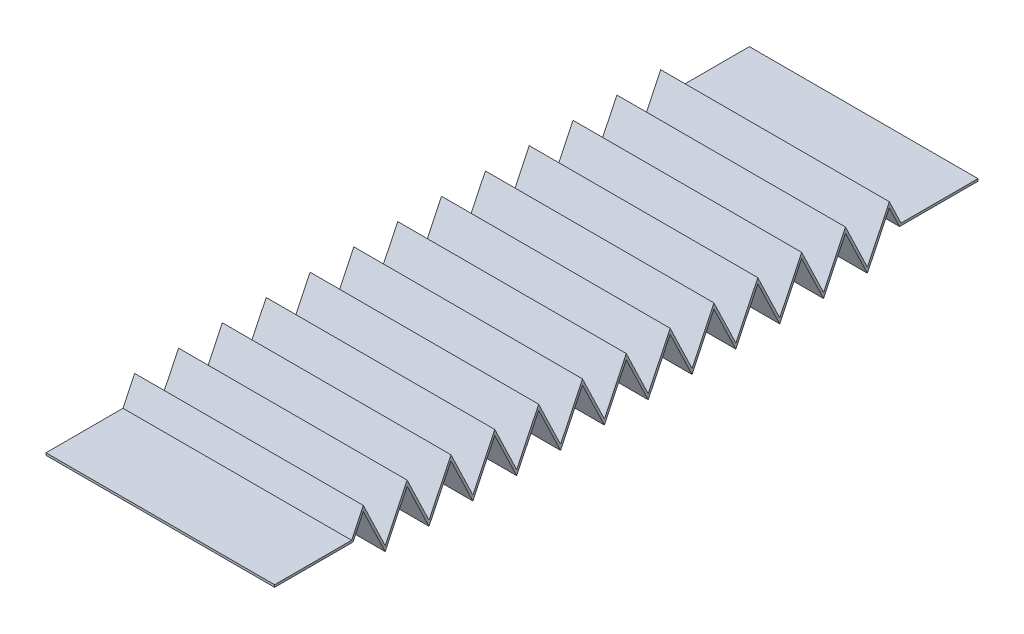
SolidWorks part; units mm, degrees
ref_plane "Front Plane" through (0, 0, 0) normal (0, 0, 1) x (1, 0, 0)
ref_plane "Top Plane" through (0, 0, 0) normal (0, 1, 0) x (1, 0, 0)
ref_plane "Right Plane" through (0, 0, 0) normal (1, 0, 0) x (0, 0, -1)
sketch "Sketch2" plane through (0, 0, 0) normal (0, 0, 1) x (1, 0, 0)
  line L1 (-27.5, 10) -> (27.5, 10)
  line L2 (-27.5, 10) -> (-27.5, 0)
  line L3 (-27.5, 0) -> (27.5, 0)
  line L4 (27.5, 10) -> (27.5, 0)
  point P4 (0, 0)
  dimension "D1" = 10
  dimension "D2" = 55
sketch "Sketch3" plane through (0, 0, 0) normal (1, 0, 0) x (0, 0, -1)
  line L0 (0, 10) -> (153.8422, 10) construction
  line L1 (0, 0) -> (153.8422, 0) construction
  line L3 (17, 5) -> (19.3968, 10)
  line L4 (19.3968, 10) -> (24.1905, 0)
  line L5 (24.1905, 0) -> (28.9842, 10)
  line L6 (28.9842, 10) -> (33.7779, 0)
  line L7 (33.7779, 0) -> (38.5716, 10)
  line L8 (38.5716, 10) -> (43.3653, 0)
  line L9 (43.3653, 0) -> (48.159, 10)
  line L10 (48.159, 10) -> (52.9527, 0)
  line L11 (52.9527, 0) -> (57.7464, 10)
  line L12 (57.7464, 10) -> (62.5401, 0)
  line L13 (62.5401, 0) -> (67.3337, 10)
  line L14 (67.3337, 10) -> (72.1274, 0)
  line L15 (72.1274, 0) -> (76.9211, 10)
  line L16 (76.9211, 10) -> (81.7148, 0)
  line L17 (81.7148, 0) -> (86.5085, 10)
  line L18 (86.5085, 10) -> (91.3022, 0)
  line L19 (0, 10) -> (0, 0) construction
  line L20 (91.3022, 0) -> (96.0959, 10)
  line L21 (96.0959, 10) -> (100.8896, 0)
  line L22 (100.8896, 0) -> (105.6833, 10)
  line L23 (105.6833, 10) -> (110.477, 0)
  line L24 (110.477, 0) -> (115.2706, 10)
  line L25 (115.2706, 10) -> (120.0643, 0)
  line L26 (120.0643, 0) -> (124.858, 10)
  line L27 (124.858, 10) -> (129.6517, 0)
  line L28 (129.6517, 0) -> (134.4454, 10)
  line L29 (134.4454, 10) -> (136.8422, 5)
  line L30 (153.8422, 10) -> (153.8422, 0) construction
  line L31 (17, 5) -> (0, 5)
  line L32 (136.8422, 5) -> (153.8422, 5)
  line L33 (153.8422, -12.75) -> (153.8422, 5.25) construction
  dimension "D2" = 17
  dimension "D1" = 10
  dimension "D3" = 17
extrude "Extrude-Thin1" add sketch "Sketch3" against normal mid plane 50 thin thin type mid plane wall 0.5
